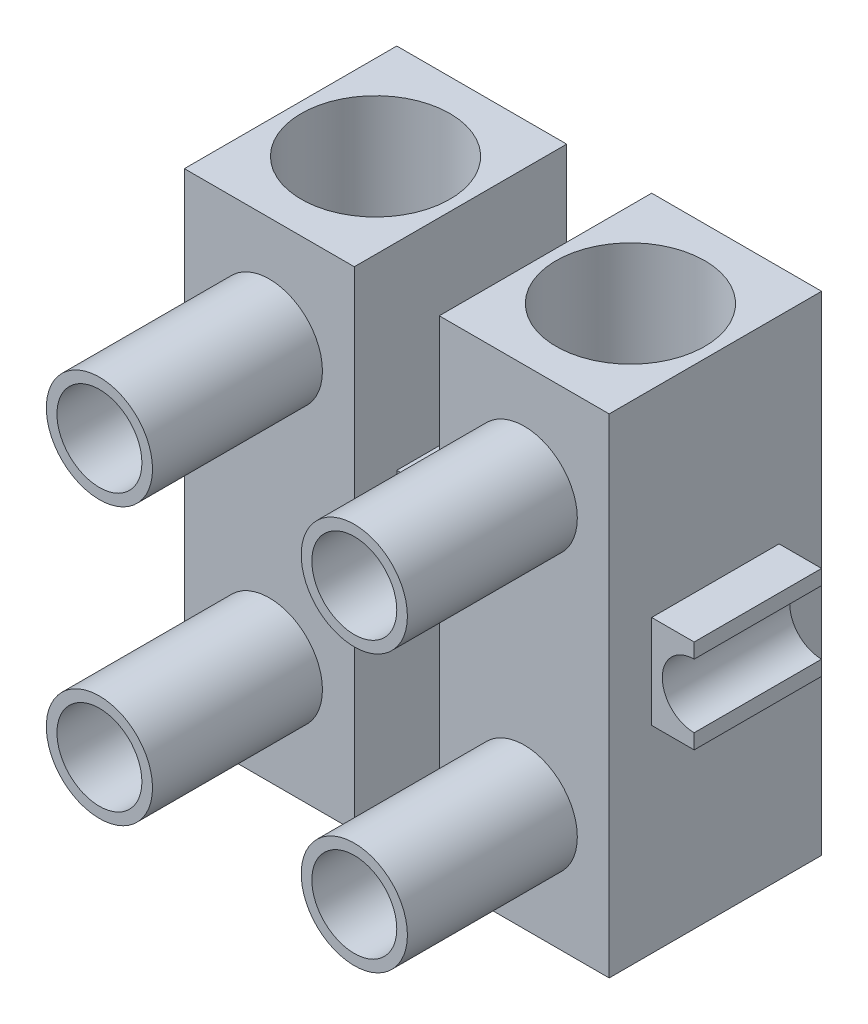
SolidWorks part; units mm, degrees
ref_plane "Alzado" through (0, 0, 0) normal (0, 0, 1) x (1, 0, 0)
ref_plane "Planta" through (0, 0, 0) normal (0, 1, 0) x (1, 0, 0)
ref_plane "Vista lateral" through (0, 0, 0) normal (1, 0, 0) x (0, 0, -1)
sketch "Croquis1" plane through (0, 0, 0) normal (0, 0, 1) x (1, 0, 0)
  line L0 (0, 0) -> (0, 23) construction
  line L1 (-4, 23) -> (4, 23)
  line L2 (4, 23) -> (4, 13.7)
  line L3 (4, 13.7) -> (6, 13.7)
  line L4 (6, 13.7) -> (6, 13)
  line L5 (6, 10) -> (6, 9.3)
  line L6 (6, 9.3) -> (4, 9.3)
  line L7 (4, 9.3) -> (4, 0)
  line L8 (4, 0) -> (-4, 0)
  line L9 (-4, 9.3) -> (-4, 0)
  line L10 (-6, 9.3) -> (-4, 9.3)
  line L11 (-6, 10) -> (-6, 9.3)
  line L12 (-6, 13.7) -> (-6, 13)
  line L13 (-4, 13.7) -> (-6, 13.7)
  line L14 (-4, 23) -> (-4, 13.7)
  line L15 (-4, 13.7) -> (-4, 9.3)
  line L16 (4, 13.7) -> (4, 9.3)
  arc A0 (6, 13) -> (6, 10) centre (6, 11.5) ccw
  arc A1 (-6, 13) -> (-6, 10) centre (-6, 11.5) cw
  dimension "D1" = 0.7
  dimension "D2" = 2
  dimension "D5" = 1.5
  dimension "D3" = 23
  dimension "D4" = 4
extrude "Saliente-Extruir1" add sketch "Croquis1" along normal blind 10 contours L8 L0 L1 L14 L15 L9 | L0 L8 L7 L16 L2 L1 region at (-2, 11.5, 0) region at (2, 11.5, 0)
extrude "Saliente-Extruir2" add sketch "Croquis1<3>" along normal blind 6 from offset 2 contours A0 L4 L3 L16 L6 L5 | L12 A1 L11 L10 L15 L13 region at (-4.0483, 11.5, 0) region at (5, 13.6517, 0)
sketch "Croquis1<3>" plane through (0, 0, 0) normal (0, 0, 1) x (1, 0, 0) same geometry as "Croquis1"
sketch "Croquis2" plane through (0, 0, 0) normal (0, -1, 0) x (1, 0, 0)
  line L0 (-4, 10) -> (0, 5) construction
  line L1 (0, 5) -> (4, 0) construction
  circle A0 centre (0, 5) radius 3.5
  dimension "D1" = 7
extrude "Cortar-Extruir1" cut sketch "Croquis2" against normal through all
sketch "Croquis3" plane through (0, 0, 10) normal (0, 0, 1) x (1, 0, 0)
  line L0 (0, 23) -> (0, 0) construction
  line L1 (-4, 23) -> (4, 23) construction
  line L2 (4, 0) -> (-4, 0) construction
  circle A0 centre (0, 5) radius 2
  circle A1 centre (0, 18) radius 2
  circle A2 centre (0, 5) radius 2.5
  circle A3 centre (0, 18) radius 2.5
  dimension "D1" = 4
  dimension "D4" = 5
  dimension "D5" = 5
  dimension "D2" = 5
  dimension "D3" = 5
extrude "Cortar-Extruir2" cut sketch "Croquis3" against normal blind 5 contours A1 L0 | L0 A1 | L0 A0 | A0 L0 region at (0.8488, 18, 10) region at (-0.8488, 18, 10) region at (0.8488, 5, 10) region at (-0.8488, 5, 10)
extrude "Saliente-Extruir3" add sketch "Croquis3<3>" along normal blind 8
sketch "Croquis3<3>" plane through (0, 0, 10) normal (0, 0, 1) x (1, 0, 0) same geometry as "Croquis3"
pattern_linear "MatrizL3" count 2 spacing 12 along (-1, 0, 0) of bodies 105
